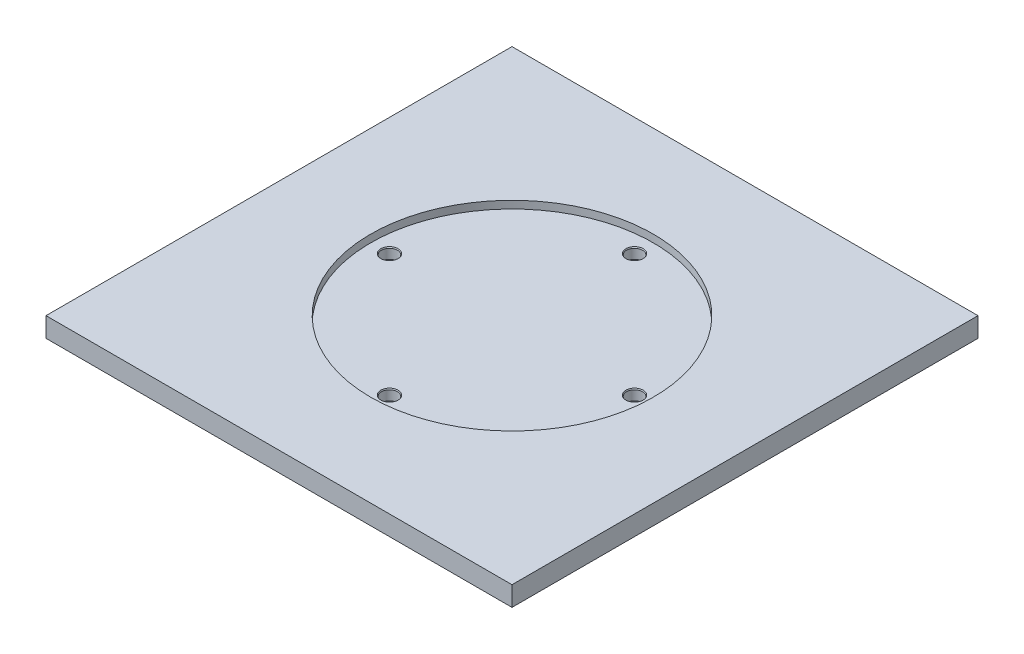
SolidWorks part; units mm, degrees
ref_plane "Front Plane" through (0, 0, 0) normal (0, 0, 1) x (1, 0, 0)
ref_plane "Top Plane" through (0, 0, 0) normal (0, 1, 0) x (1, 0, 0)
ref_plane "Right Plane" through (0, 0, 0) normal (1, 0, 0) x (0, 0, -1)
sketch "Sketch1" plane through (0, 0, 0) normal (0, 1, 0) x (1, 0, 0)
  line L1 (-77, -77) -> (77, -77)
  line L2 (-77, -77) -> (-77, 77)
  line L3 (-77, 77) -> (77, 77)
  line L4 (77, -77) -> (77, 77)
  line L5 (-77, -77) -> (77, 77) construction
  line L6 (-77, 77) -> (77, -77) construction
  point P0 (0, 0)
  dimension "D1" = 154
  dimension "D2" = 154
extrude "Boss-Extrude1" add sketch "Sketch1" along normal blind 6.5
sketch "Sketch2" plane through (0, 6.5, 0) normal (0, 1, 0) x (1, 0, 0)
  circle A0 centre (0, 0) radius 46.7
  dimension "D1" = 93.4
extrude "Cut-Extrude1" cut sketch "Sketch2" against normal blind 2.5
sketch "Sketch3" plane through (0, 4, 0) normal (0, 1, 0) x (1, 0, 0)
  circle A0 centre (0, 0) radius 40.5 construction
  circle A1 centre (0, 40.5) radius 2.65
  circle A2 centre (-40.5, 0) radius 2.65
  circle A3 centre (0, -40.5) radius 2.65
  circle A4 centre (40.5, 0) radius 2.65
  dimension "D1" = 81
  dimension "D2" = 5.3
  dimension "D3" = 5.3
  dimension "D4" = 5.3
  dimension "D5" = 5.3
extrude "Cut-Extrude2" cut sketch "Sketch3" against normal blind 3.5
chamfer "Chamfer1" distance 0.2 angle 60 4 edges at (-40.5, 4, 2.65) (0, 4, 43.15) (0, 4, -37.85) (40.5, 4, 2.65) first distance on face at (0, 4, -37.85)
